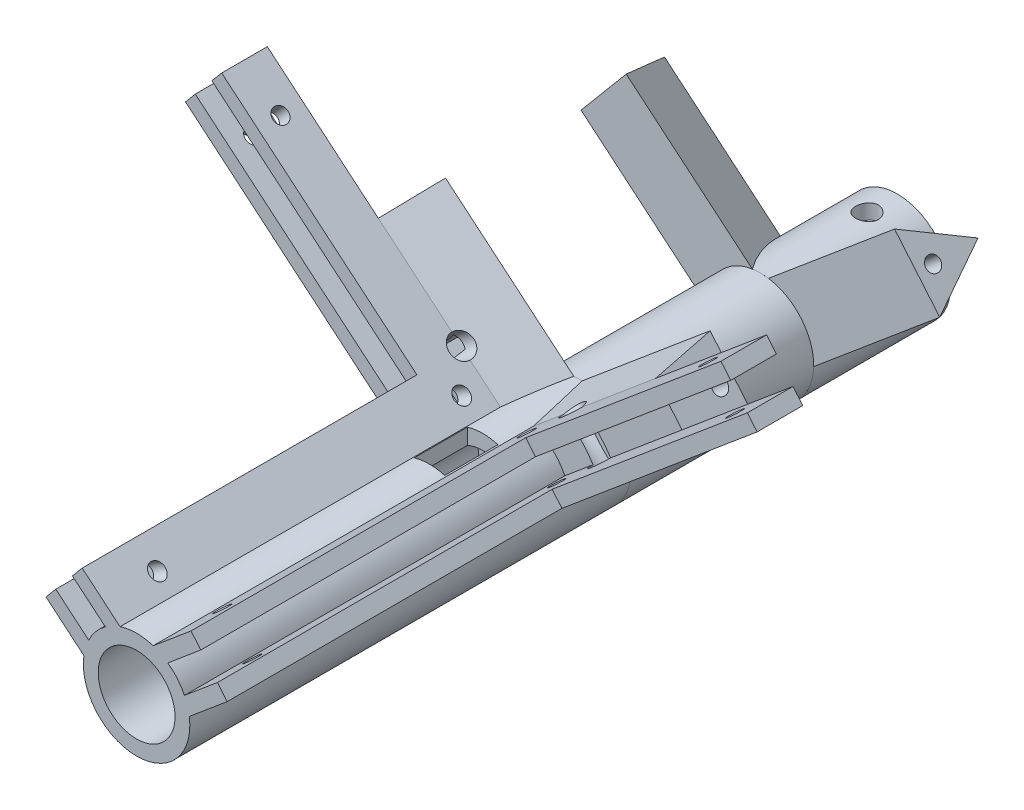
SolidWorks part; units mm, degrees
material "尼龙 101"
ref_plane "前视基准面" through (0, 0, 0) normal (0, 0, 1) x (1, 0, 0)
ref_plane "上视基准面" through (0, 0, 0) normal (0, 1, 0) x (1, 0, 0)
ref_plane "右视基准面" through (0, 0, 0) normal (1, 0, 0) x (0, 0, -1)
other "Configuration Table"
ref_plane "基准面1" through (0, 0, 10) normal (0, 0, 1) x (1, 0, 0)
sketch "草图1" plane through (0, 0, 10) normal (0, 0, 1) x (1, 0, 0)
  circle A0 centre (0, 0) radius 5.05
  circle A1 centre (0, 0) radius 7
  dimension "D1" = 10.1
  dimension "D2" = 14
extrude "凸台-拉伸1" add sketch "草图1" along normal blind 100
ref_plane "基准面2" through (0, 0, 20) normal (0, 0, 1) x (1, 0, 0)
sketch "草图2" plane through (0, 0, 20) normal (0, 0, 1) x (1, 0, 0)
  line L0 (0, -1000) -> (0, 49000) construction
  line L1 (766.0444, -642.7876) -> (-37536.1777, 31496.5929) construction
  line L2 (-766.0444, -642.7876) -> (37536.1777, 31496.5929) construction
  line L3 (0.5389, 6.9792) -> (17.3919, 21.1206)
  line L4 (6.9668, -0.6812) -> (23.8198, 13.4601)
  line L5 (17.3919, 21.1206) -> (23.8198, 13.4601)
  line L6 (-17.3919, 21.1206) -> (-23.8198, 13.4601)
  line L7 (-6.9668, -0.6812) -> (-23.8198, 13.4601)
  line L8 (-0.5389, 6.9792) -> (-17.3919, 21.1206)
  arc A0 (0.5389, 6.9792) -> (-0.5389, 6.9792) centre (0, 0) ccw
  arc A1 (-6.9668, -0.6812) -> (6.9668, -0.6812) centre (0, 0) ccw
  dimension "D1" = 14
  dimension "D2" = 50
  dimension "D3" = 50
  dimension "D4" = 10
  dimension "D5" = 22
extrude "凸台-拉伸2" add sketch "草图2" along normal blind 40
ref_plane "基准面3" through (0, 0, 0) normal (-0.6428, 0.766, 0) x (0.766, 0.6428, 0)
sketch "草图4" plane through (0, 0, 0) normal (-0.6428, 0.766, 0) x (0.766, 0.6428, 0)
  line L0 (0, -1000) -> (0, 49000) construction
  line L1 (26.899, -60) -> (26.899, -20) construction
  line L2 (6.999, -28) -> (27.999, -28)
  line L3 (6.999, -28) -> (6.999, -52)
  line L4 (6.999, -52) -> (27.999, -52)
  line L5 (27.999, -28) -> (27.999, -52)
  line L6 (6.999, -28) -> (27.999, -52) construction
  line L7 (6.999, -52) -> (27.999, -28) construction
  point P1 (17.499, -40)
  point P11 (26.899, -40)
  dimension "D1" = 9.4
  dimension "D2" = 21
  dimension "D3" = 24
revolve "切除-旋转1" cut sketch "草图4" angle 360 about L0
sketch "草图5" plane through (20.6058, 17.2903, 0) normal (0.766, 0.6428, 0) x (0, 0, -1)
  circle A0 centre (-25.9, 0) radius 0.95
  circle A1 centre (-53.9, 0) radius 0.95
  dimension "D1" = 1.9
  dimension "D2" = 1.9
extrude "切除-拉伸1" cut sketch "草图5" against normal blind 5
chamfer "倒角1" distance 5 angle 60 4 edges at (-15.3933, 6.3894, 20) (-8.9654, 14.0499, 20) (8.9654, 14.0499, 20) (15.3933, 6.3894, 20) first distance on face at (-12.5817, 10.5573, 20) first distance on face at (12.5817, 10.5573, 20)
sketch "草图7" plane through (0, 0, 60) normal (0, 0, 1) x (1, 0, 0)
  line L0 (8.1483, 9.5786) -> (10.848, 6.3612)
  line L1 (10.848, 6.3612) -> (12.1503, 7.454)
  line L2 (12.1503, 7.454) -> (9.4506, 10.6713)
  line L3 (9.4506, 10.6713) -> (8.1483, 9.5786)
  line L4 (-12.1503, 7.454) -> (-9.4506, 10.6713)
  line L5 (6.9668, -0.6812) -> (23.8198, 13.4601) construction
  line L6 (23.8198, 13.4601) -> (17.3919, 21.1206) construction
  line L7 (0, -1000) -> (0, 49000) construction
  line L8 (-10.848, 6.3612) -> (-12.1503, 7.454)
  line L9 (-8.1483, 9.5786) -> (-10.848, 6.3612)
  line L10 (-9.4506, 10.6713) -> (-8.1483, 9.5786)
  dimension "D1" = 4.2
  dimension "D2" = 1.7
  dimension "D3" = 2.9
  dimension "D4" = 12.8
extrude "切除-拉伸2" cut sketch "草图7" against normal blind 10
chamfer "倒角3" distance 8 distance2 1.3 4 edges at (15.3933, 6.3894, 60) (8.9654, 14.0499, 60) (-15.3933, 6.3894, 60) (-8.9654, 14.0499, 60) first distance on face at (15.3933, 6.3894, 56) first distance on face at (8.9654, 14.0499, 56) first distance on face at (-15.3933, 6.3894, 56) first distance on face at (-8.9654, 14.0499, 56)
sketch "草图10" plane through (0, 0, 60) normal (0, 0, 1) x (1, 0, 0)
  line L0 (2.1737, 6.654) -> (32.8155, 32.3655)
  line L1 (6.9303, 0.9852) -> (37.5721, 26.6967)
  line L2 (18.2275, 20.1247) -> (2.1737, 6.654) construction
  line L3 (32.8155, 32.3655) -> (37.5721, 26.6967)
  line L4 (4.109, 5.6671) -> (34.101, 30.8334)
  line L5 (6.2945, 3.0625) -> (36.2865, 28.2288)
  line L6 (0, -1000) -> (0, 49000) construction
  line L7 (-32.8155, 32.3655) -> (-37.5721, 26.6967)
  line L8 (-6.9303, 0.9852) -> (-37.5721, 26.6967)
  line L9 (-6.2945, 3.0625) -> (-36.2865, 28.2288)
  line L10 (-4.109, 5.6671) -> (-34.101, 30.8334)
  line L11 (-2.1737, 6.654) -> (-32.8155, 32.3655)
  circle A0 centre (0, 0) radius 7
  line M6 (8.1483, 9.5786) -> (9.4506, 10.6713)
  line M7 (9.4506, 10.6713) -> (12.1503, 7.454)
  line M8 (12.1503, 7.454) -> (10.848, 6.3612)
  line M9 (10.848, 6.3612) -> (8.1483, 9.5786)
  arc M10 (2.1737, 6.654) -> (6.9303, 0.9852) centre (0, 0) cw
  line M11 (6.9303, 0.9852) -> (22.9841, 14.456)
  line M12 (22.9841, 14.456) -> (18.2275, 20.1247)
  line M13 (18.2275, 20.1247) -> (2.1737, 6.654)
  dimension "D1" = 14
  dimension "D2" = 40
  dimension "D3" = 2
  dimension "D4" = 2
extrude "凸台-拉伸4" add sketch "草图10" along normal blind 6 contours L4 M10 M9 M6 M7 M12 M13 | L4 L3 L0 M12 | L5 L1 L3 M12 | L5 M10 M11 M12 M7 M8 M9 | A0 L11 L7 L10 | A0 L9 L7 L8 | L4 M9 M7 M6 | L5 M9 M8 M7 region at (11.0592, 12.8311, 60) region at (26.1643, 25.479, 60) region at (-18.3205, 18.902, 60) region at (8.928, 9.9718, 60) region at (14.5566, 8.6631, 60) region at (29.6353, 21.3424, 60) region at (11.3706, 7.0608, 60) region at (-21.7961, 14.7599, 60)
sketch "草图11" plane through (0, 0, 66) normal (0, 0, 1) x (1, 0, 0)
  line L0 (2.1737, 6.654) -> (7.153, 10.8321)
  line L1 (32.8155, 32.3655) -> (2.1737, 6.654) construction
  line L2 (7.153, 10.8321) -> (11.9096, 5.1633)
  line L3 (6.9303, 0.9852) -> (37.5721, 26.6967) construction
  line L4 (11.9096, 5.1633) -> (6.9303, 0.9852)
  line L5 (4.109, 5.6671) -> (8.4386, 9.3)
  line L6 (4.109, 5.6671) -> (34.101, 30.8334) construction
  line L7 (6.2945, 3.0625) -> (10.624, 6.6954)
  line L8 (6.2945, 3.0625) -> (36.2865, 28.2288) construction
  line L9 (0, -1000) -> (0, 49000) construction
  line L10 (-7.153, 10.8321) -> (-11.9096, 5.1633)
  line L11 (-11.9096, 5.1633) -> (-6.9303, 0.9852)
  line L12 (-6.2945, 3.0625) -> (-10.624, 6.6954)
  line L13 (-4.109, 5.6671) -> (-8.4386, 9.3)
  line L14 (-2.1737, 6.654) -> (-7.153, 10.8321)
  circle A0 centre (0, 0) radius 7
  arc M8 (-6.9303, 0.9852) -> (-6.2945, 3.0625) centre (0, 0) cw
  line M9 (-6.2945, 3.0625) -> (-36.2865, 28.2288)
  line M11 (-37.5721, 26.6967) -> (-6.9303, 0.9852)
  dimension "D1" = 14
  dimension "D2" = 6.5
extrude "凸台-拉伸5" add sketch "草图11" along normal through all contours A0 L5 L2 L0 | A0 L4 L2 L7 | A0 L14 L10 L13 | L10 M9 M11 M8 region at (5.4733, 8.1477, 66) region at (-5.4733, 8.1477, 66) region at (8.9744, 3.9753, 66) region at (-8.9744, 3.9753, 66)
sketch "草图13" plane through (0, 0, 0) normal (-0.6428, 0.766, 0) x (0.766, 0.6428, 0)
  line L0 (12.399, -60) -> (14.099, -60) construction
  line L1 (0, -999.3806) -> (0, 49000.6194) construction
  circle A0 centre (13.249, -60) radius 1.5
  dimension "D1" = 3
revolve "切除-旋转2" cut sketch "草图13" angle 360 about L1
sketch "草图14" plane through (-20.6058, 17.2903, 0) normal (-0.766, 0.6428, 0) x (0, 0, 1)
  circle A0 centre (26.1, -0.3812) radius 0.95
  circle A1 centre (54.1, -0.3812) radius 0.95
  dimension "D1" = 1.9
  dimension "D2" = 1.9
extrude "切除-拉伸3" cut sketch "草图14" against normal blind 5
sketch "草图15" plane through (0, 0, 0) normal (0, 1, 0) x (1, 0, 0)
  line L1 (-2, -64.5) -> (2, -64.5)
  line L2 (-2, -64.5) -> (-2, -71.5)
  line L3 (-2, -71.5) -> (2, -71.5)
  line L4 (2, -64.5) -> (2, -71.5)
  line L5 (-2, -64.5) -> (2, -71.5) construction
  line L6 (-2, -71.5) -> (2, -64.5) construction
  circle A0 centre (0, -14) radius 1.5
  point P3 (0, -68)
  dimension "D1" = 3
  dimension "D2" = 4
  dimension "D3" = 7
  dimension "D4" = 68
extrude "切除-拉伸4" cut sketch "草图15" along normal through all
sketch "草图16" plane through (0, 0, 0) normal (-0.6428, 0.766, 0) x (0.766, 0.6428, 0)
  line L0 (0, -1000) -> (0, 49000) construction
  circle A0 centre (39.9422, -63) radius 1
  circle A1 centre (9.4422, -63) radius 1
  circle A2 centre (9.4422, -103) radius 1
  dimension "D1" = 2
  dimension "D2" = 2
  dimension "D3" = 2
revolve "切除-旋转3" cut sketch "草图16" angle 360 about L0
